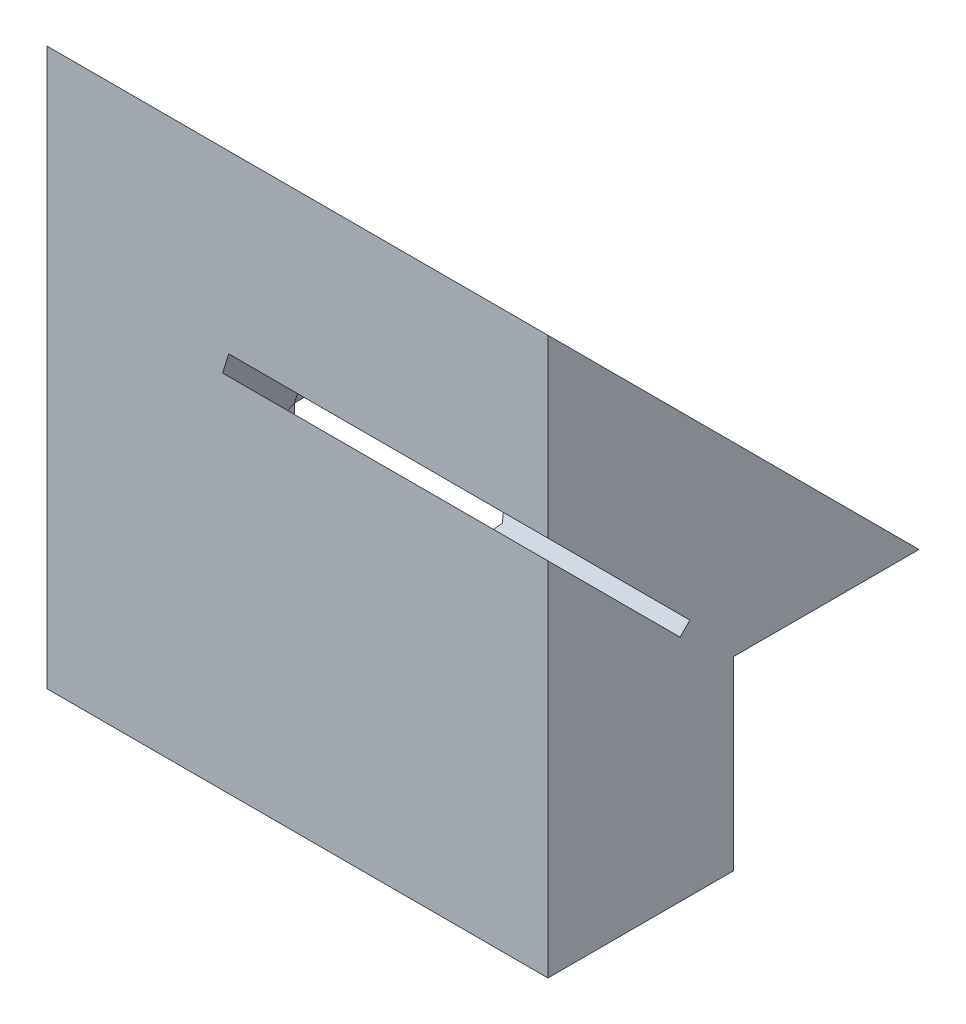
SolidWorks part; units mm, degrees
ref_plane "Front Plane" through (0, 0, 0) normal (0, 0, 1) x (1, 0, 0)
ref_plane "Top Plane" through (0, 0, 0) normal (0, 1, 0) x (1, 0, 0)
ref_plane "Right Plane" through (0, 0, 0) normal (1, 0, 0) x (0, 0, -1)
sketch "Sketch1" plane through (0, 0, 0) normal (0, 0, 1) x (1, 0, 0)
  line L1 (-25, 10) -> (25, 10)
  line L2 (-25, 10) -> (-25, -10)
  line L3 (-25, -10) -> (25, -10)
  line L4 (25, 10) -> (25, -10)
  line L5 (-25, 10) -> (25, -10) construction
  line L6 (-25, -10) -> (25, 10) construction
  point P1 (0, 0)
  dimension "D1" = 50
  dimension "D2" = 20
extrude "Boss-Extrude1" add sketch "Sketch1" along normal blind 10
ref_plane "Plane1" through (0, -5, 5) normal (0, -0.7071, 0.7071) x (1, 0, 0)
sketch "Sketch2" plane through (0, -5, 5) normal (0, -0.7071, 0.7071) x (1, 0, 0)
  line L0 (-23, -10.0711) -> (35.3756, 5.5706)
  line L1 (29.1639, 28.7528) -> (-10.4391, 18.1413)
  line L2 (-25, -7.0711) -> (25, -7.0711) construction
  line L3 (-23, -10.0711) -> (-10.4391, 18.1413)
  line L4 (-25, 0) -> (-25, -7.0711) construction
  line L5 (29.1639, 28.7528) -> (35.3756, 5.5706)
  line L6 (19.5046, 26.1646) -> (44.4889, 8.0125) construction
  line L7 (44.4889, 8.0125) -> (35.3756, 5.5706) construction
  point P1 (0, 0)
  point P4 (0, 0)
  dimension "D1" = 24
  dimension "D2" = 15
  dimension "D3" = 51
  dimension "D4" = 3
  dimension "D5" = 2
  dimension "D6" = 41
  dimension "D7" = 31
  dimension "D8" = 51
  dimension "D9" = 69.8696
extrude "Cut-Extrude1" cut sketch "Sketch2" against normal mid plane 0.75
sketch "Sketch3" plane through (0, -10, 0) normal (0, -1, 0) x (1, 0, 0)
  line L8 (-25, 0) -> (-21.6643, 0)
  line L9 (-21.6643, 0) -> (-21.4974, 0.5303)
  line L10 (-21.4974, 0.5303) -> (-10.4043, 0.5303)
  line L11 (-10.4043, 0.5303) -> (-11.8038, 0)
  line L12 (-11.8038, 0) -> (25, 0)
  line L13 (25, 0) -> (25, 10)
  line L14 (25, 10) -> (-25, 10)
  line L15 (-25, 10) -> (-25, 0)
  line L16 (-25, 0) -> (-21.6643, 0)
  line L17 (-21.6643, 0) -> (-21.4974, 0.5303)
  line L18 (-21.4974, 0.5303) -> (-10.4043, 0.5303)
  line L19 (-10.4043, 0.5303) -> (-11.8038, 0)
  line L20 (-11.8038, 0) -> (25, 0)
  line L21 (25, 0) -> (25, 10)
  line L22 (25, 10) -> (-25, 10)
  line L23 (-25, 10) -> (-25, 0)
  dimension "D1" = 0
sketch "Sketch4" plane through (0, 0, 0) normal (0, 0, -1) x (-1, 0, 0)
  line L8 (10.4043, -9.4697) -> (21.4974, -9.4697)
  line L9 (21.4974, -9.4697) -> (21.6643, -10)
  line L10 (21.6643, -10) -> (25, -10)
  line L11 (25, -10) -> (25, 10)
  line L12 (25, 10) -> (-25, 10)
  line L13 (-25, 10) -> (-25, -10)
  line L14 (-25, -10) -> (11.8038, -10)
  line L15 (11.8038, -10) -> (10.4043, -9.4697)
  line L16 (10.4043, -9.4697) -> (21.4974, -9.4697)
  line L17 (21.4974, -9.4697) -> (21.6643, -10)
  line L18 (21.6643, -10) -> (25, -10)
  line L19 (25, -10) -> (25, 10)
  line L20 (25, 10) -> (-25, 10)
  line L21 (-25, 10) -> (-25, -10)
  line L22 (-25, -10) -> (11.8038, -10)
  line L23 (11.8038, -10) -> (10.4043, -9.4697)
  dimension "D1" = 0
extrude "Boss-Extrude3" add sketch "Sketch3" along normal blind 10
extrude "Boss-Extrude4" add sketch "Sketch4" along normal blind 10
sketch "Sketch5" plane through (0, -20, 0) normal (0, -1, 0) x (1, 0, 0)
  line L0 (2, 16.3561) -> (2, -14.5386)
  line L1 (2, -14.5386) -> (27.687, -14.5386)
  line L2 (27.687, -14.5386) -> (27.687, 16.3561)
  line L3 (27.687, 16.3561) -> (2, 16.3561)
  dimension "D1" = 2
extrude "Cut-Extrude3" cut sketch "Sketch5" against normal through all contours L3 L0 L1 L2
sketch "Sketch6" plane through (2, 0, 0) normal (1, 0, 0) x (0, 0, -1)
  line L0 (-10, 10) -> (10, -10)
  line L1 (10, -10) -> (10, 10)
  line L2 (10, 10) -> (10, -10) construction
  line L3 (-10, 10) -> (10, 10) construction
  line L4 (10, 10) -> (-10, 10)
extrude "Cut-Extrude4" cut sketch "Sketch6" against normal through all
fillet "Fillet1" radius 2 1 edges at (-11.8038, -10, -5)
fillet "Fillet2" radius 2 1 edges at (-11.8038, -15, 0)
